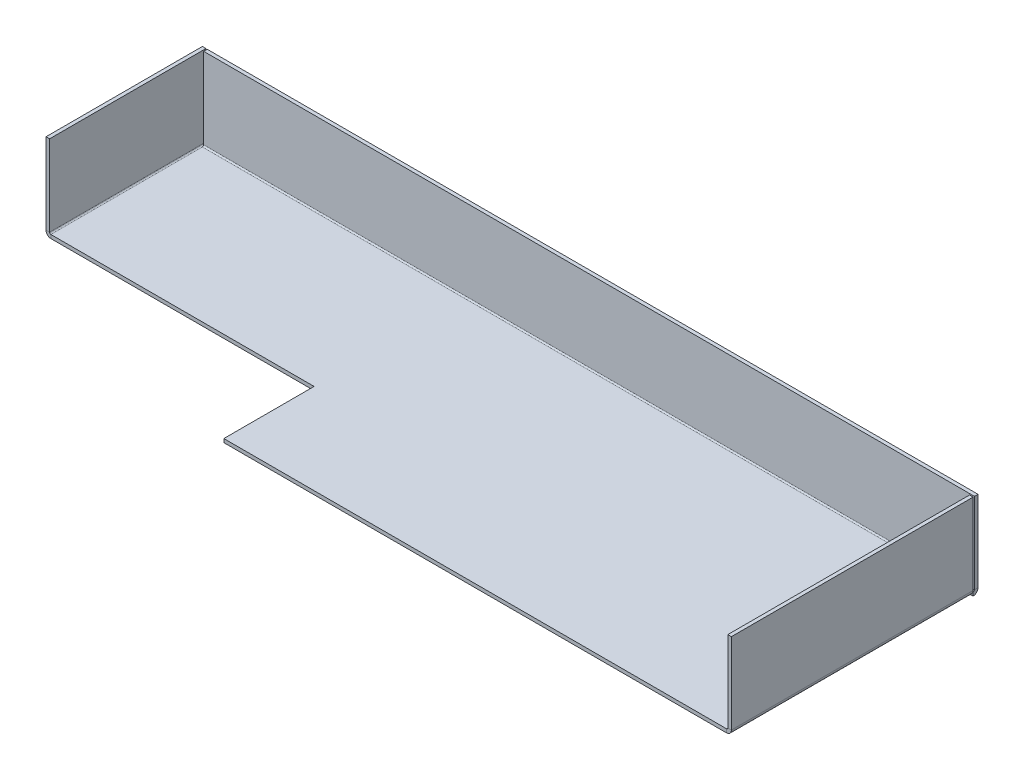
SolidWorks part; units mm, degrees
note: The reader was unsure of these and kept them because the rebuilt part matched: flange length of "Brida de arista1", "Brida de arista2", "Brida de arista3".
material "AISI 316L Acero inoxidable"
ref_plane "Alzado" through (0, 0, 0) normal (0, 0, 1) x (1, 0, 0)
ref_plane "Planta" through (0, 0, 0) normal (0, 1, 0) x (1, 0, 0)
ref_plane "Vista lateral" through (0, 0, 0) normal (1, 0, 0) x (0, 0, -1)
sketch "Croquis1" plane through (0, 0, 0) normal (0, 1, 0) x (1, 0, 0)
  line L0 (-220, -21.5) -> (220, -21.5) construction
  line L1 (-220, -72) -> (220, -72) construction
  line L2 (-220, -72) -> (-220, 72) construction
  line L3 (-220, 72) -> (220, 72) construction
  line L4 (220, -72) -> (220, 72) construction
  line L5 (-220, -72) -> (220, 72) construction
  line L6 (-220, 72) -> (220, -72) construction
  line L7 (-70, -72) -> (-70, 72) construction
  line L8 (-220, 72) -> (-220, -21.5) construction
  line L9 (-220, -21.5) -> (-70, -21.5) construction
  line L10 (-70, -21.5) -> (-70, -72) construction
  line L11 (-70, -72) -> (220, -72) construction
  line L12 (-67, -69) -> (217, -69)
  line L13 (217, -69) -> (217, 69)
  line L14 (-217, 69) -> (217, 69)
  line L15 (-217, 69) -> (-217, -18.5)
  line L16 (-217, -18.5) -> (-67, -18.5)
  line L17 (-67, -18.5) -> (-67, -69)
  point P0 (0, 0)
  dimension "D1" = 440
  dimension "D2" = 144
  dimension "D3" = 93.5
  dimension "D4" = 150
  dimension "D5" = 3
base flange "Brida base1" sketch "Croquis1" thickness 2 reverse thickness direction no parameters "D1"=0.7366
edge flange "Brida de arista1" sketch "Croquis8" flange angle 90 flange length 48 flange position material inside bend radius 0.7366 thickness 2 relief rectangular parameters "D6"=10
sketch "Croquis8" plane through (-217, 0, 0) normal (-1, 0, 0) x (0, 0, 1)
  line L0 (-69, 0) -> (18.5, 0) construction
  line L1 (-69, 0) -> (18.5, 0)
  line L2 (-69, 0) -> (-69, 46)
  line L3 (-69, 46) -> (18.5, 46)
  line L4 (18.5, 46) -> (18.5, 0)
bend "Pliegue de arista1" bend radius 0.7366 bend angle 90 parameters "D5"=1
edge flange "Brida de arista2" sketch "Croquis11" flange angle 90 flange length 48 flange position material inside bend radius 0.7366 thickness 2 relief none parameters "D6"=10
sketch "Croquis11" plane through (0, 0, -69) normal (0, 0, -1) x (-1, 0, 0)
  line L0 (-217, 0) -> (214.2634, 0) construction
  line L1 (-217, 0) -> (214.2634, 0)
  line L2 (-217, 0) -> (-217, 46)
  line L3 (-217, 46) -> (214.2634, 46)
  line L4 (214.2634, 46) -> (214.2634, 0)
bend "Pliegue de arista2" bend radius 0.7366 bend angle 90 parameters "D5"=2
edge flange "Brida de arista3" sketch "Croquis23" flange angle 90 flange length 48 flange position material inside bend radius 0.7366 thickness 2 relief none parameters "D6"=10, "D8"=1
sketch "Croquis23" plane through (217, 0, 0) normal (1, 0, 0) x (0, 0, -1)
  line L0 (-69, 0) -> (66.2634, 0) construction
  line L1 (-69, 0) -> (66.2634, 0)
  line L2 (-69, 0) -> (-69, 46)
  line L3 (-69, 46) -> (66.2634, 46)
  line L4 (66.2634, 46) -> (66.2634, 0)
bend "Pliegue de arista6" bend radius 0.7366 bend angle 90 parameters "D5"=6
sketch "Líneas de pliegue1" [suppressed] plane through (0, 0, 0) normal (0, 1, 0) x (1, 0, 0)
sketch "Cuadro delimitador1" [suppressed] plane through (0, 0, 0) normal (0, 1, 0) x (1, 0, 0)
sheet metal parameters "Chapa metálica1" thickness 2 parameters "D1"=0.7366
flat pattern "Chapa desplegada1" [suppressed]
sketch "Líneas de pliegue2" plane through (0, 0, 0) normal (0, 1, 0) x (1, 0, 0)
sketch3d "Cuadro delimitador2" [suppressed]
  line L0 (-217, -69, 0) -> (217, -69, 0) construction
  line L1 (-217, 69, 0) -> (217, 69, 0) construction
  line L2 (-217, -69, 0) -> (-217, 69, 0) construction
  line L3 (217, -69, 0) -> (217, 69, 0) construction
sheet metal parameters "Chapa metálica2" thickness 2 parameters "D1"=0.7366
flat pattern "Chapa desplegada1" [suppressed]
sketch "Líneas de pliegue2" plane through (0, 0, 0) normal (0, 1, 0) x (1, 0, 0)
  line L0 (-215.6273, 69) -> (-215.6273, -18.5) construction
  line L1 (-215.6273, 69) -> (-215.6273, -18.5) construction
sketch3d "Cuadro delimitador2" [suppressed]
  line L0 (217, -69, 0) -> (-265.7546, -69, 0) construction
  line L1 (217, 69, 0) -> (-265.7546, 69, 0) construction
  line L2 (217, -69, 0) -> (217, 69, 0) construction
  line L3 (-265.7546, -69, 0) -> (-265.7546, 69, 0) construction
bend of the flat pattern "Aplanar-<Pliegue de arista1>1"
sheet metal parameters "Chapa metálica3" thickness 2 parameters "D1"=0.7366
flat pattern "Chapa desplegada1" [suppressed]
sketch "Líneas de pliegue2" plane through (0, 0, 0) normal (0, 1, 0) x (1, 0, 0)
  line L0 (-215.6273, 69) -> (-215.6273, -18.5) construction
  line L1 (-215.6273, 69) -> (-215.6273, -18.5) construction
  line L2 (217, 67.6273) -> (-214.2634, 67.6273) construction
  line L3 (217, 67.6273) -> (-214.2634, 67.6273) construction
sketch3d "Cuadro delimitador2" [suppressed]
  line L0 (217, -69, 0) -> (-262.2546, -69, 0) construction
  line L1 (217, 114.2546, 0) -> (-262.2546, 114.2546, 0) construction
  line L2 (217, -69, 0) -> (217, 114.2546, 0) construction
  line L3 (-262.2546, -69, 0) -> (-262.2546, 114.2546, 0) construction
bend of the flat pattern "Aplanar-<Pliegue de arista2>1"
bend of the flat pattern "Aplanar-<Pliegue de arista1>1"
sheet metal parameters "Chapa metálica4" thickness 2 parameters "D1"=0.7366
flat pattern "Chapa desplegada1"
sketch "Líneas de pliegue2" plane through (0, 0, 0) normal (0, 1, 0) x (1, 0, 0)
  line L0 (-215.6273, 69) -> (-215.6273, -18.5) construction
  line L1 (-215.6273, 69) -> (-215.6273, -18.5) construction
  line L2 (217, 67.6273) -> (-214.2634, 67.6273) construction
  line L3 (217, 67.6273) -> (-214.2634, 67.6273) construction
  line L4 (215.6257, -69) -> (215.6322, 66.2634) construction
  line L8 (215.6257, -69) -> (215.6322, 66.2634) construction
sketch3d "Cuadro delimitador2" [suppressed]
  line L0 (262.2546, -69, 0) -> (-262.2546, -69, 0) construction
  line L1 (262.2546, 114.2546, 0) -> (-262.2546, 114.2546, 0) construction
  line L2 (262.2546, -69, 0) -> (262.2546, 114.2546, 0) construction
  line L3 (-262.2546, -69, 0) -> (-262.2546, 114.2546, 0) construction
bend of the flat pattern "Aplanar-<Pliegue de arista2>1"
bend of the flat pattern "Aplanar-<Pliegue de arista6>1"
bend of the flat pattern "Aplanar-<Pliegue de arista1>1"
